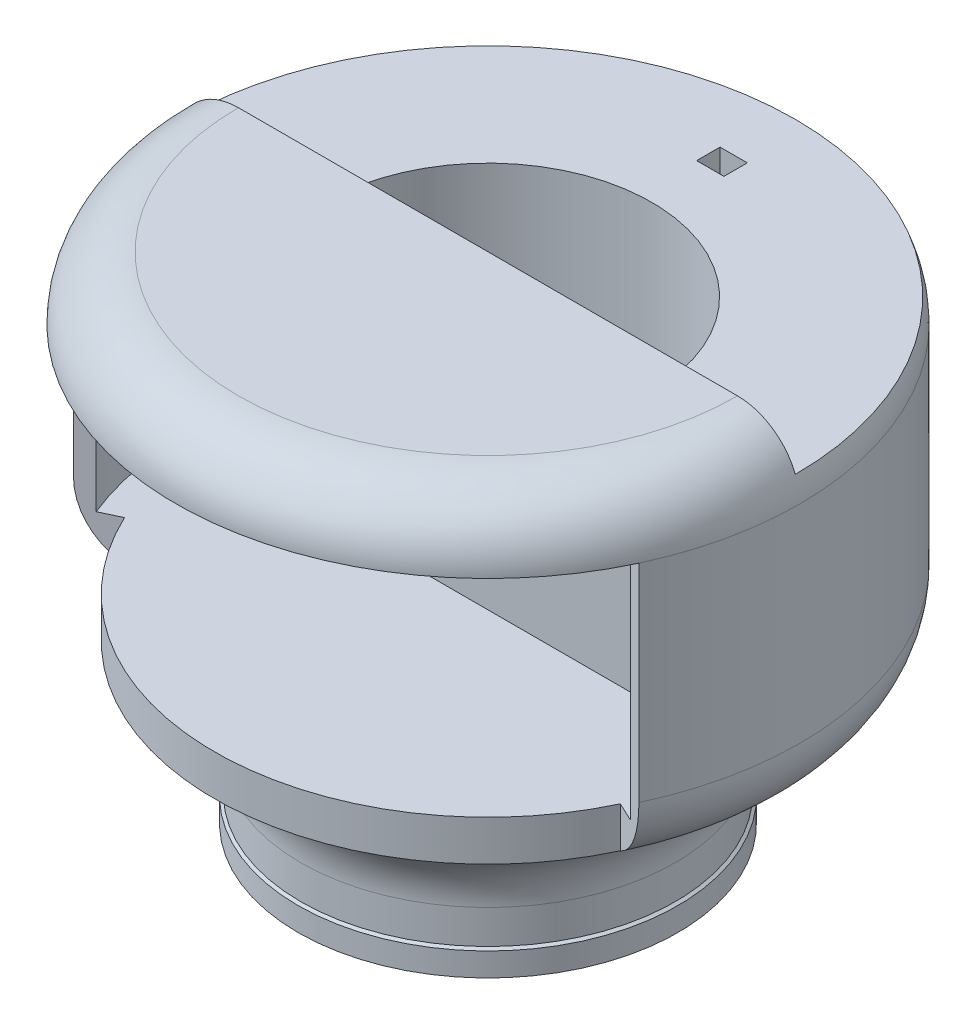
SolidWorks part; units mm, degrees
ref_plane "Front Plane" through (0, 0, 0) normal (0, 0, 1) x (1, 0, 0)
ref_plane "Top Plane" through (0, 0, 0) normal (0, 1, 0) x (1, 0, 0)
ref_plane "Right Plane" through (0, 0, 0) normal (1, 0, 0) x (0, 0, -1)
sketch "Sketch1" plane through (0, 0, 0) normal (0, 0, 1) x (1, 0, 0)
  line L0 (0, 0) -> (0, 90.2242) construction
  line L28 (0, 63.4279) -> (32, 63.4279)
  line L29 (40, 55.4279) -> (40, 28.8468)
  line L30 (22.5, 0) -> (24.35, 0)
  line L31 (24.35, 0) -> (24.35, 3)
  line L32 (24.35, 3) -> (24, 3.25)
  line L33 (24, 3.25) -> (24, 7.5811)
  line L34 (28.5399, 15.9588) -> (35.4601, 20.4691)
  line L35 (0, 13) -> (22, 13)
  line L36 (22.5, 12.5) -> (22.5, 0)
  line L37 (0, 13) -> (0, 63.4279)
  arc A0 (22, 13) -> (22.5, 12.5) centre (22, 12.5) cw
  arc A1 (24, 7.5811) -> (28.5399, 15.9588) centre (34, 7.5811) cw
  arc A2 (35.4601, 20.4691) -> (40, 28.8468) centre (30, 28.8468) ccw
  arc A3 (32, 63.4279) -> (40, 55.4279) centre (32, 55.4279) cw
  point P11 (22.9, 63.4279)
  point P18 (22.5, 13)
  point P21 (24, 13)
  point P24 (40, 23.4279)
  point P27 (40, 63.4279)
  point P28 (28.5604, 23.4279)
  point P31 (22.5, 17)
  dimension "D8" = 9.75
  dimension "D9" = 0.5
  dimension "D4" = 1.85
  dimension "D1" = 22.5
  dimension "D10" = 10
  dimension "D11" = 10
  dimension "D12" = 8
  dimension "D2" = 40
  dimension "D3" = 40
  dimension "D5" = 1.5
  dimension "D6" = 3
  dimension "D7" = 13
revolve "Revolve1" add sketch "Sketch1" angle 360 about L0
ref_plane "Plane1" through (0, 13, 0) normal (0, -1, 0) x (-1, 0, 0)
sketch "Sketch18" plane through (0, 0, 0) normal (0, 0, 1) x (1, 0, 0)
  line L0 (0, 0) -> (0, 101.5813) construction
  line L1 (-24.35, 0) -> (24.35, 0) construction
sketch "Sketch3" plane through (0, 0, 0) normal (0, 0, 1) x (1, 0, 0)
  point P0 (1.2404, 19.1989)
ref_point "Point1"
ref_plane "Plane2" through (0, 0, 22.9) normal (0, 0, 1) x (1, 0, 0)
ref_plane "Plane3" through (0, 0, 40) normal (0, 0, 1) x (1, 0, 0)
ref_plane "Plane4" through (0, 55.4279, 0) normal (0, 1, 0) x (1, 0, 0)
sketch "Sketch9" plane through (0, 55.4279, 0) normal (0, 1, 0) x (1, 0, 0)
  line L1 (-24, -1.7631) -> (24, -1.7631)
  arc A2 (-37, -1.6015) -> (37, -2.3985) centre (0, -2) ccw
  arc A3 (-37, -1.6015) -> (37, -2.3985) centre (0, -2) cw
  arc A6 (-24, -1.7631) -> (24, -1.7631) centre (0, -0.0603) cw
  dimension "D1" = 74
  dimension "D3" = 13
  dimension "D4" = 13
ref_plane "Plane5" through (0, 13, 0) normal (0, -1, 0) x (-1, 0, 0)
sketch "Sketch11" plane through (0, 13, 0) normal (0, -1, 0) x (-1, 0, 0)
  line L0 (-21, 0) -> (21, 0)
  arc A1 (-21, 0) -> (21, 0) centre (0, 0) cw
  dimension "D1" = 42
extrude "Cut-Extrude3" cut sketch "Sketch11" against normal blind 60
ref_plane "Plane6" through (0, 0, -40) normal (0, 0, -1) x (-1, 0, 0)
extrude "Cut-Extrude5" cut sketch "Sketch9" against normal blind 30 and the other way blind 2
sketch "Sketch19" plane through (0, 0, 0) normal (1, 0, 0) x (0, 0, -1)
  line L0 (-47.0647, 55.4279) -> (-35.0647, 55.4279)
  line L1 (31.2976, 55.4279) -> (-31.2976, 55.4279) construction
  line L2 (-35.0647, 55.4279) -> (-35.0647, 18.9279)
  line L3 (-35.0647, 18.9279) -> (-47.0647, 18.9279)
  line L4 (-47.0647, 18.9279) -> (-47.0647, 55.4279)
  dimension "D1" = 12
  dimension "D2" = 36.5
revolve "Cut-Revolve2" cut sketch "Sketch19" angle 65 about L0 other way angle 65
ref_plane "Plane7" through (0, 0, 22.5) normal (0, 0, -1) x (-1, 0, 0)
sketch "Sketch21" plane through (0, 0, 22.5) normal (0, 0, -1) x (-1, 0, 0)
  line L0 (0, 0) -> (0, 101.5813) construction
  line L1 (-1.625, 4) -> (1.625, 4)
  line L2 (-1.625, 4) -> (-1.625, 0)
  line L3 (-1.625, 0) -> (1.625, 0)
  line L4 (1.625, 4) -> (1.625, 0)
  line L5 (-1.625, 4) -> (1.625, 0) construction
  line L6 (-1.625, 0) -> (1.625, 4) construction
  line L7 (-22.5, 0) -> (22.5, 0) construction
  point P0 (0, 2)
  dimension "D1" = 4
  dimension "D2" = 3.25
extrude "Boss-Extrude3" add sketch "Sketch21" along normal blind 1.35
pattern_circular "CirPattern1" count 5 over 360 about axis through (0, 0, 0) along (0, -1, 0) of "Boss-Extrude3"
ref_plane "Plane8" through (0, 20.4691, 0) normal (0, 1, 0) x (1, 0, 0)
sketch "Sketch22" plane through (0, 63.4279, 0) normal (0, 1, 0) x (1, 0, 0)
  line L0 (-40, 0) -> (40, 0)
  arc A0 (-40, 0) -> (40, 0) centre (0, 0) cw
  arc A1 (36.2523, -16.9047) -> (-36.2523, -16.9047) centre (0, 0) ccw construction
extrude "Cut-Extrude9" cut sketch "Sketch22" against normal blind 5
sketch "Sketch23" plane through (0, 0, -40) normal (0, 0, -1) x (-1, 0, 0)
  line L0 (0, 0) -> (0, 101.5813) construction
  line L1 (44, 55.4279) -> (-44, 55.4279) construction
  circle A0 centre (0, 42.1379) radius 10
  dimension "D1" = 20
  dimension "D2" = 13.29
extrude "Cut-Extrude10" cut sketch "Sketch23" against normal blind 10
fillet "Fillet1" radius 5 1 edges at (1.8994, 32.3199, -34.9534)
sketch "Sketch24" plane through (0, 58.4279, 0) normal (0, 1, 0) x (1, 0, 0)
  line L1 (-6, 32.5) -> (6, 32.5)
  line L2 (-6, 32.5) -> (-6, 27.5)
  line L3 (-6, 27.5) -> (6, 27.5)
  line L4 (6, 32.5) -> (6, 27.5)
  line L5 (-6, 32.5) -> (6, 27.5) construction
  line L6 (-6, 27.5) -> (6, 32.5) construction
  arc A0 (39.4162, 0) -> (-39.4162, 0) centre (0, 0) ccw construction
  point P0 (0, 30)
  dimension "D1" = 30
  dimension "D2" = 5
  dimension "D3" = 12
extrude "Boss-Extrude4" add sketch "Sketch24" against normal blind 8
sketch "Sketch26" plane through (0, 58.4279, 0) normal (0, 1, 0) x (1, 0, 0)
  line L1 (-1.75, 31.5) -> (1.75, 31.5)
  line L2 (-1.75, 31.5) -> (-1.75, 28.5)
  line L3 (-1.75, 28.5) -> (1.75, 28.5)
  line L4 (1.75, 31.5) -> (1.75, 28.5)
  line L5 (-1.75, 31.5) -> (1.75, 28.5) construction
  line L6 (-1.75, 28.5) -> (1.75, 31.5) construction
  arc A0 (39.4162, 0) -> (-39.4162, 0) centre (0, 0) ccw construction
  point P0 (0, 30)
  dimension "D1" = 30
  dimension "D2" = 3
  dimension "D3" = 3.5
extrude "Cut-Extrude11" cut sketch "Sketch26" against normal blind 10
sketch "Sketch27" plane through (6, 0, 0) normal (1, 0, 0) x (0, 0, -1)
  line L0 (32.5, 50.4279) -> (32.5, 57.4279) construction
  line L1 (28.0394, 56.918) -> (31.9606, 56.918)
  line L2 (28.0394, 56.918) -> (28.0394, 50.9378)
  line L3 (28.0394, 50.9378) -> (31.9606, 50.9378)
  line L4 (31.9606, 56.918) -> (31.9606, 50.9378)
  line L5 (28.0394, 56.918) -> (31.9606, 50.9378) construction
  line L6 (28.0394, 50.9378) -> (31.9606, 56.918) construction
  line L7 (27.5, 50.4279) -> (27.5, 57.4279) construction
  line L8 (27.5, 50.4279) -> (32.5, 50.4279) construction
  point P0 (30, 53.9279)
  dimension "D1" = 5
  dimension "D2" = 3.5
extrude "Cut-Extrude12" cut sketch "Sketch27" against normal blind 5
ref_plane "Plane9" through (-39.4162, 58.4279, 0) normal (0.375, 0.927, 0) x (0.927, -0.375, 0)
ref_plane "Plane10" through (0, 58.4279, 0) normal (0, 1, 0) x (1, 0, 0)
